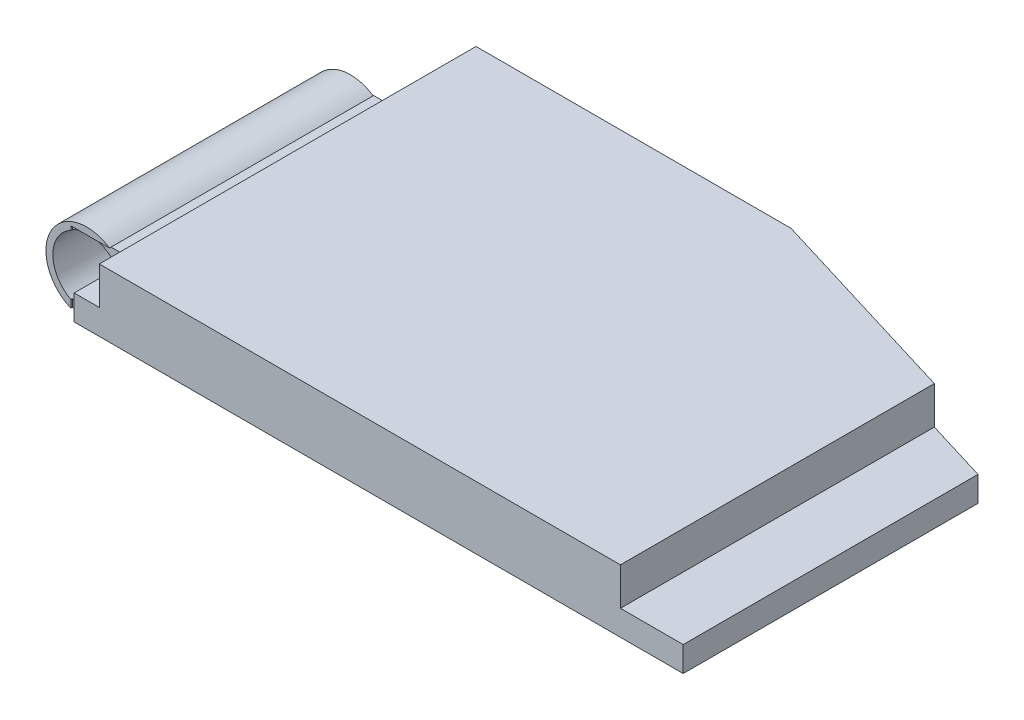
SolidWorks part; units mm, degrees
ref_plane "Front Plane" through (0, 0, 0) normal (0, 0, 1) x (1, 0, 0)
ref_plane "Top Plane" through (0, 0, 0) normal (0, 1, 0) x (1, 0, 0)
ref_plane "Right Plane" through (0, 0, 0) normal (1, 0, 0) x (0, 0, -1)
sketch "Sketch1" plane through (0, 0, 0) normal (0, 1, 0) x (1, 0, 0)
  line L1 (0, 0) -> (52, 0)
  line L2 (0, 0) -> (0, -30)
  line L3 (0, -30) -> (52, -30)
  line L4 (52, 0) -> (52, -30)
  dimension "D1" = 52
  dimension "D2" = 30
extrude "Boss-Extrude1" add sketch "Sketch1" along normal blind 2
sketch "Sketch3" plane through (0, 0, 0) normal (0, -1, 0) x (1, 0, 0)
  line L0 (0, 30) -> (52, 30) construction
  line L1 (23, 17.6) -> (29, 17.6)
  line L2 (23, 17.6) -> (23, 14.6)
  line L3 (23, 14.6) -> (29, 14.6)
  line L4 (29, 17.6) -> (29, 14.6)
  line L5 (52, 30) -> (52, 0) construction
  dimension "D1" = 12.4
  dimension "D2" = 3
  dimension "D3" = 6
  dimension "D4" = 29
extrude "Boss-Extrude3" add sketch "Sketch3" along normal blind 7
sketch "Sketch4" plane through (0, 0, 17.6) normal (0, 0, 1) x (1, 0, 0)
  line L0 (29, -7) -> (23, -7) construction
  circle A0 centre (26, -4) radius 1
  point P5 (26, -7)
  dimension "D1" = 2
  dimension "D2" = 3
extrude "Cut-Extrude1" cut sketch "Sketch4" against normal through all
ref_plane "Plane1" through (0, 0, 15) normal (0, 0, 1) x (1, 0, 0)
sketch "Sketch5" plane through (0, 0, 15) normal (0, 0, 1) x (1, 0, 0)
  line L0 (0, 2) -> (52, 2) construction
  circle A0 centre (0, -0.7) radius 2.7
  circle A1 centre (0, -0.7) radius 3.25
  dimension "D1" = 5.4
  dimension "D2" = 6.5
extrude "Boss-Extrude4" add sketch "Sketch5" along normal blind 10.5 and the other way blind 10.5 separate body
sketch "Sketch6" plane through (0, 0, 30) normal (0, 0, 1) x (1, 0, 0)
  circle A0 centre (0, -0.7) radius 2.7
  circle A1 centre (0, -0.7) radius 2.7 construction
extrude "Cut-Extrude2" cut sketch "Sketch6" against normal through all
sketch "Sketch7" plane through (0, 2, 0) normal (0, 1, 0) x (1, 0, 0)
  line L0 (0, 0) -> (0, -30) construction
  line L1 (-1.2698, -25.3698) -> (3.5, -25.3698)
  line L2 (-1.2698, -25.3698) -> (-1.2698, -30.2241)
  line L3 (-1.2698, -30.2241) -> (3.5, -30.2241)
  line L4 (3.5, -25.3698) -> (3.5, -30.2241)
  line L5 (0, -4.4599) -> (3.5, -4.4599)
  line L6 (0, -4.4599) -> (0, 2.762)
  line L7 (0, 2.762) -> (3.5, 2.762)
  line L8 (3.5, -4.4599) -> (3.5, 2.762)
  dimension "D1" = 3.5
extrude "Cut-Extrude3" cut sketch "Sketch7" against normal through all
sketch "Sketch8" plane through (0, 2, 0) normal (0, 1, 0) x (1, 0, 0)
  line L0 (52, 0) -> (3.5, 0) construction
  line L1 (47, 0) -> (5.5, 0)
  line L2 (47, 0) -> (47, -30)
  line L3 (47, -30) -> (5.5, -30)
  line L4 (5.5, 0) -> (5.5, -30)
  line L5 (3.5, -30) -> (52, -30) construction
  line L6 (52, -30) -> (52, 0) construction
  line L7 (3.5, -30) -> (3.5, -25.3698) construction
  dimension "D1" = 5
  dimension "D2" = 2
extrude "Boss-Extrude5" add sketch "Sketch8" along normal blind 3
sketch "Sketch9" plane through (0, 0, 0) normal (0, -1, 0) x (1, 0, 0)
  line L0 (30.5839, 0) -> (52, 6.5236)
  line L1 (52, 0) -> (3.5, 0) construction
  line L2 (52, 30) -> (52, 0) construction
  line L3 (52, 6.5236) -> (52, -3.8456)
  line L4 (52, -3.8456) -> (30.5839, -3.8456)
  line L5 (30.5839, -3.8456) -> (30.5839, 0)
extrude "Cut-Extrude4" cut sketch "Sketch9" against normal through all
